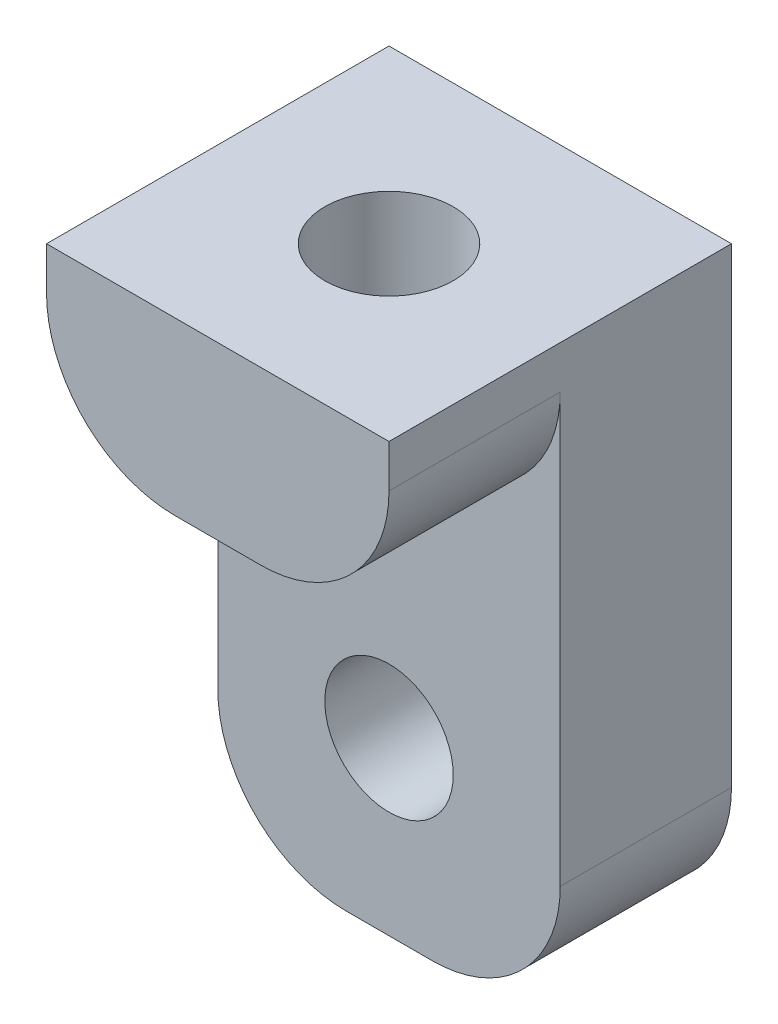
SolidWorks part; units mm, degrees
material "ABS"
ref_plane "Front Plane" through (0, 0, 0) normal (0, 0, 1) x (1, 0, 0)
ref_plane "Top Plane" through (0, 0, 0) normal (0, 1, 0) x (1, 0, 0)
ref_plane "Right Plane" through (0, 0, 0) normal (1, 0, 0) x (0, 0, -1)
sketch "Sketch1" plane through (0, 0, 0) normal (0, 0, 1) x (1, 0, 0)
  line L1 (-20, 50) -> (20, 50)
  line L2 (-20, 50) -> (-20, -20)
  line L3 (-20, -20) -> (20, -20)
  line L4 (20, 50) -> (20, -20)
  circle A0 centre (0, 0) radius 7.5
  point P9 (0, -20)
  dimension "D1" = 15
  dimension "D2" = 20
  dimension "D3" = 70
  dimension "D4" = 40
extrude "Boss-Extrude1" add sketch "Sketch1" along normal blind 40
sketch "Sketch2" plane through (0, 50, 0) normal (0, 1, 0) x (1, 0, 0)
  line L0 (-20, 0) -> (20, -40) construction
  line L4 (20, 0) -> (-20, 0)
  line L5 (-20, 0) -> (-20, -40)
  line L6 (-20, -40) -> (20, -40)
  line L7 (20, -40) -> (20, 0)
  line L8 (20, 0) -> (-20, 0)
  line L9 (-20, 0) -> (-20, -40)
  line L10 (-20, -40) -> (20, -40)
  line L11 (20, -40) -> (20, 0)
  circle A0 centre (0, -20) radius 7.5
  dimension "D2" = 15
  dimension "D1" = 0
extrude "Cut-Extrude1" cut sketch "Sketch2" against normal blind 20 contours L0 A0 | A0 L0 region at (2.2508, 50, 17.7492) region at (-2.2508, 50, 22.2508)
sketch "Sketch3" plane through (0, 0, 40) normal (0, 0, 1) x (1, 0, 0)
  line L0 (20, -20) -> (20, 50) construction
  line L1 (-20, -20) -> (20, -20)
  line L2 (-20, -20) -> (-20, 30)
  line L3 (-20, 30) -> (20, 30)
  line L4 (20, -20) -> (20, 30)
  dimension "D1" = 50
extrude "Cut-Extrude2" cut sketch "Sketch3" against normal blind 20 contours L2 L3 L4 L1
fillet "Fillet1" radius 15 4 edges at (-20, 30, 30) (20, 30, 30) (20, -20, 10) (-20, -20, 10)
